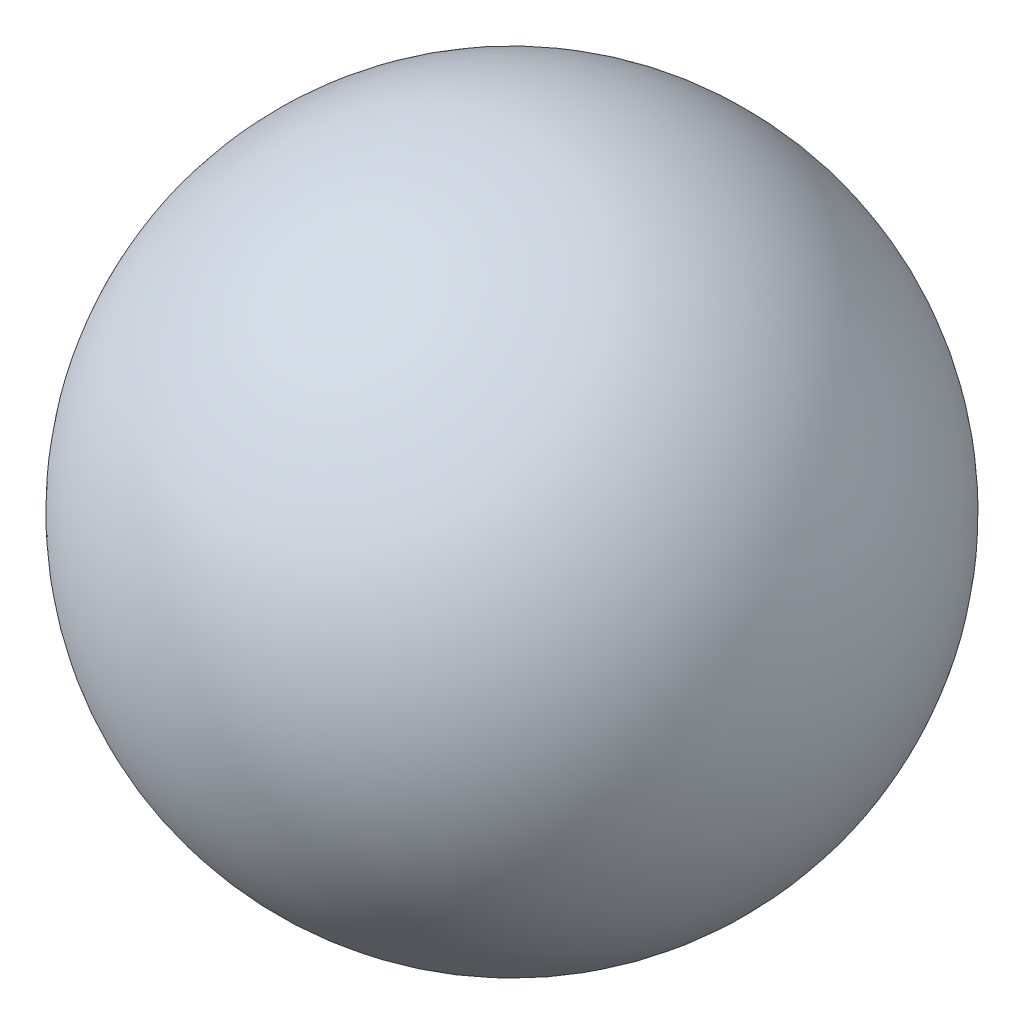
SolidWorks part; units mm, degrees
material "AISI 4130 钢，正火温度为 870C"
ref_plane "前视基准面" through (0, 0, 0) normal (0, 0, 1) x (1, 0, 0)
ref_plane "上视基准面" through (0, 0, 0) normal (0, 1, 0) x (1, 0, 0)
ref_plane "右视基准面" through (0, 0, 0) normal (1, 0, 0) x (0, 0, -1)
sketch "草图1" plane through (0, 0, 0) normal (0, 0, 1) x (1, 0, 0)
  line L0 (-6.1743, 0) -> (7.0455, 0) construction
  line L1 (-4.5, 0) -> (4.5, 0)
  arc A0 (4.5, 0) -> (-4.5, 0) centre (0, 0) ccw
  dimension "D1" = 4.5
revolve "旋转3" add sketch "草图1" angle 360 about L0
ref_axis "基准轴1" through (0, 0, 4.4) along (0, 0, -1)
